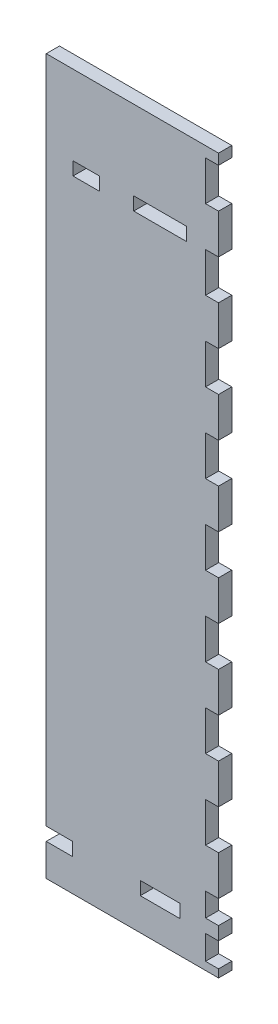
SolidWorks part; units mm, degrees
material "Balsa"
ref_plane "Plan de face" through (0, 0, 0) normal (0, 0, 1) x (1, 0, 0)
ref_plane "Plan de dessus" through (0, 0, 0) normal (0, 1, 0) x (1, 0, 0)
ref_plane "Plan de droite" through (0, 0, 0) normal (1, 0, 0) x (0, 0, -1)
sketch "Esquisse1" plane through (0, 0, 0) normal (0, 0, 1) x (1, 0, 0)
  line L1 (65.1211, 0) -> (0, 0)
  line L2 (65.1211, 0) -> (65.1211, 270)
  line L3 (65.1211, 270) -> (0, 270)
  line L4 (0, 0) -> (0, 270)
  dimension "D1" = 270
  dimension "D2" = 65.1211
extrude "Boss.-Extru.1" add sketch "Esquisse1" against normal blind 5
sketch "Esquisse2" plane through (0, 0, 0) normal (0, 0, 1) x (1, 0, 0)
  line L0 (0, 270) -> (0, 0) construction
  line L1 (0, 17.15) -> (10, 17.15)
  line L2 (0, 17.15) -> (0, 12.15)
  line L3 (0, 12.15) -> (10, 12.15)
  line L4 (10, 17.15) -> (10, 12.15)
  line L5 (65.1211, 0) -> (65.1211, 270) construction
  line L6 (50.5493, 17.15) -> (35.5493, 17.15)
  line L7 (50.5493, 17.15) -> (50.5493, 12.15)
  line L8 (50.5493, 12.15) -> (35.5493, 12.15)
  line L9 (35.5493, 17.15) -> (35.5493, 12.15)
  line L10 (65.1211, 12.15) -> (60.2011, 12.15)
  line L11 (65.1211, 12.15) -> (65.1211, 3)
  line L12 (65.1211, 3) -> (60.2011, 3)
  line L13 (60.2011, 12.15) -> (60.2011, 3)
  line L14 (0, 0) -> (65.1211, 0) construction
  line L15 (65.1211, 0) -> (65.1211, 270) construction
  line L16 (65.1211, 17.15) -> (60.2011, 17.15)
  line L17 (65.1211, 17.15) -> (65.1211, 26)
  line L18 (65.1211, 26) -> (60.2011, 26)
  line L19 (60.2011, 17.15) -> (60.2011, 26)
  line L20 (65.1211, 270) -> (0, 270) construction
  line L21 (65.1211, 266) -> (60.2011, 266)
  line L22 (65.1211, 266) -> (65.1211, 251)
  line L23 (65.1211, 251) -> (60.2011, 251)
  line L24 (60.2011, 266) -> (60.2011, 251)
  line L25 (65.1211, 236) -> (60.2011, 236)
  line L26 (65.1211, 236) -> (65.1211, 221)
  line L27 (65.1211, 221) -> (60.2011, 221)
  line L28 (60.2011, 236) -> (60.2011, 221)
  line L29 (65.1211, 206) -> (60.2011, 206)
  line L30 (65.1211, 206) -> (65.1211, 191)
  line L31 (65.1211, 191) -> (60.2011, 191)
  line L32 (60.2011, 206) -> (60.2011, 191)
  line L33 (65.1211, 176) -> (60.2011, 176)
  line L34 (65.1211, 176) -> (65.1211, 161)
  line L35 (65.1211, 161) -> (60.2011, 161)
  line L36 (60.2011, 176) -> (60.2011, 161)
  line L37 (65.1211, 146) -> (60.2011, 146)
  line L38 (65.1211, 146) -> (65.1211, 131)
  line L39 (65.1211, 131) -> (60.2011, 131)
  line L40 (60.2011, 146) -> (60.2011, 131)
  line L41 (65.1211, 116) -> (60.2011, 116)
  line L42 (65.1211, 116) -> (65.1211, 101)
  line L43 (65.1211, 101) -> (60.2011, 101)
  line L44 (60.2011, 116) -> (60.2011, 101)
  line L45 (65.1211, 86) -> (60.2011, 86)
  line L46 (65.1211, 86) -> (65.1211, 71)
  line L47 (65.1211, 71) -> (60.2011, 71)
  line L48 (60.2011, 86) -> (60.2011, 71)
  line L49 (65.1211, 56) -> (60.2011, 56)
  line L50 (65.1211, 56) -> (65.1211, 41)
  line L51 (65.1211, 41) -> (60.2011, 41)
  line L52 (60.2011, 56) -> (60.2011, 41)
  line L54 (10.1211, 240) -> (20.1211, 240)
  line L55 (10.1211, 240) -> (10.1211, 235)
  line L56 (10.1211, 235) -> (20.1211, 235)
  line L57 (20.1211, 240) -> (20.1211, 235)
  line L59 (33.0493, 235) -> (53.0493, 235)
  line L60 (33.0493, 235) -> (33.0493, 240)
  line L61 (33.0493, 240) -> (53.0493, 240)
  line L62 (53.0493, 235) -> (53.0493, 240)
  dimension "D1" = 3
  dimension "D2" = 4.92
  dimension "D3" = 9.15
  dimension "D4" = 12.15
  dimension "D5" = 5
  dimension "D6" = 5
  dimension "D7" = 15
  dimension "D8" = 5
  dimension "D9" = 15
  dimension "D10" = 4
  dimension "D12" = 30
  dimension "D13" = 10
  dimension "D14" = 20
  dimension "D15" = 55
  dimension "D16" = 5
  dimension "D17" = 12.0718
  dimension "D18" = 30
  dimension "D11" = 8
extrude "Enlèv. mat.-Extru.1" cut sketch "Esquisse2" against normal blind 5
